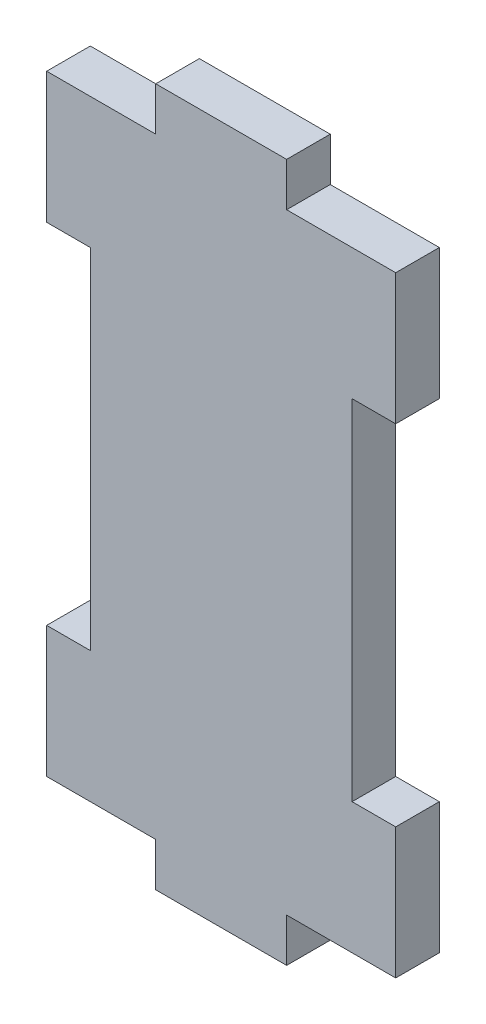
SolidWorks part; units mm, degrees
material "Acrylic (Medium-high impact)"
ref_plane "Front Plane" through (0, 0, 0) normal (0, 0, 1) x (1, 0, 0)
ref_plane "Top Plane" through (0, 0, 0) normal (0, 1, 0) x (1, 0, 0)
ref_plane "Right Plane" through (0, 0, 0) normal (1, 0, 0) x (0, 0, -1)
sketch "Sketch2" plane through (0, 0, 0) normal (0, 0, 1) x (1, 0, 0)
  line L0 (-7.5, 40) -> (7.5, 40)
  line L1 (7.5, 40) -> (7.5, 35)
  line L2 (7.5, 35) -> (20, 35)
  line L3 (20, 35) -> (20, -35)
  line L4 (0, 0) -> (20, 0) construction
  line L5 (0, -40) -> (0, 40) construction
  line L6 (-20, 35) -> (-20, -35)
  line L7 (-7.5, 35) -> (-20, 35)
  line L8 (-7.5, 40) -> (-7.5, 35)
  line L9 (-7.5, -40) -> (-7.5, -35)
  line L10 (-7.5, -35) -> (-20, -35)
  line L11 (7.5, -35) -> (20, -35)
  line L12 (7.5, -40) -> (7.5, -35)
  line L13 (-7.5, -40) -> (7.5, -40)
  point P2 (0, 0)
  point P17 (-20, 0)
  dimension "D1" = 5
  dimension "D2" = 20
  dimension "D3" = 7.5
  dimension "D4" = 40
extrude "Boss-Extrude2" add sketch "Sketch2" along normal blind 5
sketch "Sketch3" plane through (0, 0, 5) normal (0, 0, 1) x (1, 0, 0)
  line L0 (0, 0) -> (-20, 0) construction
  line L1 (-20, 35) -> (-20, -35) construction
  line L3 (-15, -20) -> (-20, -20)
  line L4 (-15, -20) -> (-15, 20)
  line L5 (-15, 20) -> (-20, 20)
  line L6 (-20, -20) -> (-20, 20)
  line L7 (-15, -20) -> (-20, 20) construction
  line L8 (-15, 20) -> (-20, -20) construction
  point P5 (-17.5, 0)
  point P8 (-20, 0)
  dimension "D1" = 40
  dimension "D2" = 5
extrude "Cut-Extrude1" cut sketch "Sketch3" against normal blind 5
mirror "Mirror1" about plane through (0, 0, 0) normal (1, 0, 0) of "Cut-Extrude1"
